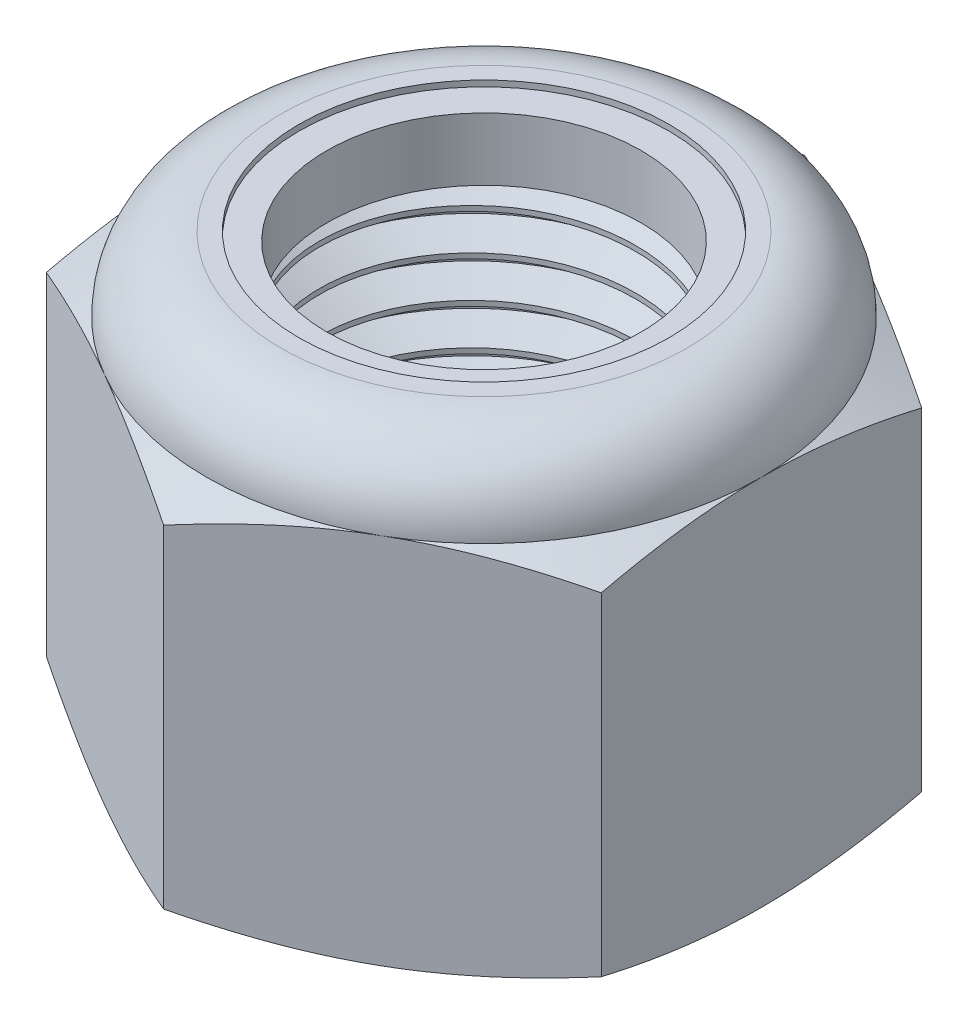
SolidWorks part; units mm, degrees
ref_plane "Front" through (0, 0, 0) normal (0, 0, 1) x (1, 0, 0)
ref_plane "Top" through (0, 0, 0) normal (0, 1, 0) x (1, 0, 0)
ref_plane "Right" through (0, 0, 0) normal (1, 0, 0) x (0, 0, -1)
sketch "Sketch1" plane through (0, 0, 0) normal (1, 0, 0) x (0, 0, -1)
  line L0 (0, 0) -> (0, 11.5094) construction
  line L1 (7.1437, 0) -> (-7.1437, 0) construction
  line L2 (-4.7625, 11.5094) -> (4.7625, 11.5094) construction
  line L3 (4.7625, 11.5094) -> (4.7625, 10.451) construction
  point P9 (-4.7625, 11.5094)
  point P10 (4.7625, 11.5094)
  point P11 (7.1437, 0)
  dimension "Height" = 11.5094
  dimension "Hex Flats" = 14.2875
  dimension "Thread Dia" = 9.525
  dimension "Thread Pitch" = 1.0583
sketch "Sketch13" plane through (0, 0, 0) normal (0, 1, 0) x (1, 0, 0)
  line L1 (0, 8.2489) -> (-7.1438, 4.1244)
  line L2 (-7.1438, 4.1244) -> (-7.1437, -4.1244)
  line L3 (-7.1437, -4.1244) -> (0, -8.2489)
  line L4 (0, -8.2489) -> (7.1438, -4.1244)
  line L5 (7.1438, -4.1244) -> (7.1438, 4.1244)
  line L6 (7.1438, 4.1244) -> (0, 8.2489)
  circle A0 centre (0, 0) radius 7.1437 construction
  circle A1 centre (0, 0) radius 4.7625
  point P11 (0, -4.7625)
  point P13 (0, 4.7625)
extrude "Extrude1" add sketch "Sketch13" along normal up to vertex (11.5094 mm away) up to point (0, 11.5094, 0)
sketch "Sketch5" plane through (0, 0, 0) normal (1, 0, 0) x (0, 0, -1)
  line L0 (0, 0) -> (7.1437, 0)
  line L1 (7.1437, 0) -> (8.2489, 0.5153)
  line L2 (8.2489, 0.5153) -> (8.2489, 9.0758)
  line L3 (8.2489, 9.0758) -> (7.1437, 9.5911)
  line L4 (5.2255, 11.5094) -> (5.2255, 12.7794)
  line L5 (5.2255, 12.7794) -> (9.5189, 12.7794)
  line L6 (9.5189, 12.7794) -> (9.5189, -1.27)
  line L7 (9.5189, -1.27) -> (0, -1.27)
  line L8 (0, -1.27) -> (0, 0)
  line L9 (7.1437, 9.5911) -> (7.1437, 0) construction
  line L12 (8.2489, 11.5094) -> (8.2489, 0) construction
  line L13 (8.2489, 5.7547) -> (9.5189, 5.7547) construction
  line L15 (0, 0) -> (0, 12.7794) construction
  line L18 (7.1437, 0) -> (-7.1437, 0) construction
  line L19 (4.1244, 11.5094) -> (8.2489, 11.5094) construction
  line L20 (0, 12.7794) -> (5.2255, 12.7794) construction
  line L21 (4.1244, 0) -> (8.2489, 0) construction
  arc A0 (7.1437, 9.5911) -> (5.2255, 11.5094) centre (5.2255, 9.5911) ccw
  dimension "D1" = 25
  dimension "D2" = 1.27
  dimension "D4" = 1.9182
revolve "Cut-Revolve3" cut sketch "Sketch5" angle 360 about L15
sketch "Sketch4" plane through (0, 0, 0) normal (1, 0, 0) x (0, 0, -1)
  line L0 (0, 9.5911) -> (5.2388, 9.5911)
  line L1 (5.2388, 9.5911) -> (0, 7.1483)
  line L3 (0, 2.4429) -> (5.2388, 0)
  line L4 (5.2388, 0) -> (0, 0)
  line L5 (0, 0) -> (0, 9.5911) construction
  line L10 (0, 0) -> (0, 11.5094) construction
  line L11 (0, 2.4429) -> (0, 0)
  line L12 (0, 9.5911) -> (0, 7.1483)
  line L13 (6.1867, 9.5911) -> (0, 9.5911) construction
  dimension "D1" = 25
  dimension "D2" = 10.4775
sketch "Sketch6" plane through (0, 0, 0) normal (1, 0, 0) x (0, 0, -1)
  line L0 (0, 9.5911) -> (6.9914, 9.5911)
  line L1 (5.2255, 11.357) -> (2.6128, 11.357)
  line L2 (0, 12.7794) -> (0, 9.5911)
  line L3 (2.6128, 12.7794) -> (0, 12.7794)
  line L4 (0, 12.7794) -> (5.2255, 12.7794) construction
  line L5 (0, 0) -> (0, 12.7794) construction
  line L6 (0, 12.7794) -> (0, 0) construction
  line L7 (2.6128, 11.357) -> (2.6128, 12.7794)
  line L8 (5.2255, 11.5094) -> (5.2255, 11.357) construction
  line L9 (2.6128, 11.357) -> (0, 11.357) construction
  line L10 (0, 11.357) -> (0, 7.1483) construction
  arc A0 (6.9914, 9.5911) -> (5.2255, 11.357) centre (5.2255, 9.5911) ccw
  arc A1 (7.1437, 9.5911) -> (5.2255, 11.5094) centre (5.2255, 9.5911) ccw construction
  dimension "D1" = 0.1524
revolve "Cut-Revolve4" cut sketch "Sketch6" angle 360 about L6
revolve "Cut-Revolve2" cut sketch "Sketch4" angle 360 about L5
sketch "Sketch7" plane through (0, 0, 0) normal (1, 0, 0) x (0, 0, -1)
  line L0 (4.0481, 9.6673) -> (6.9134, 9.6673)
  line L1 (5.2255, 11.2808) -> (4.0481, 11.2808)
  line L2 (4.0481, 11.2808) -> (4.0481, 9.6673)
  line L3 (4.0481, 9.6673) -> (0, 9.6673) construction
  line L4 (0, 9.6673) -> (0, 11.2808) construction
  line L5 (0, 11.2808) -> (4.0481, 11.2808) construction
  line L6 (4.0481, 9.6673) -> (4.0481, 9.5911) construction
  line L7 (0, 9.5911) -> (6.9914, 9.5911) construction
  line L8 (5.2255, 11.2808) -> (5.2255, 11.357) construction
  arc A0 (6.9134, 9.6673) -> (5.2255, 11.2808) centre (5.2255, 9.5911) ccw
  arc A2 (6.9914, 9.5911) -> (5.2255, 11.357) centre (5.2255, 9.5911) ccw construction
  point P15 (4.0481, 11.2808)
  point P18 (-4.6368, 11.2808)
  point P19 (4.6368, 11.2808)
  dimension "D1" = 0.0762
  dimension "D2" = 8.0962
revolve "Revolve2" add sketch "Sketch7" angle 360 about L4
sketch "Sketch2" plane through (0, 0, 0) normal (1, 0, 0) x (0, 0, -1)
  line L0 (-4.7625, 0) -> (-4.7625, 9.5911) construction
  line L1 (0, 0) -> (4.7625, 0)
  line L2 (0, 0) -> (0, 9.5911)
  line L3 (0, 9.5911) -> (4.7625, 9.5911)
  line L4 (4.7625, 0) -> (4.7625, 9.5911)
  line L6 (6.1867, 9.5911) -> (7.1437, 9.5911) construction
  line L7 (0, -4.7625) -> (0, 0) construction
revolve "Revolve1" add sketch "Sketch2" angle 360 about L7
sketch "Sketch9" plane through (0, 0, 0) normal (1, 0, 0) x (0, 0, -1)
  line L0 (4.8771, 10.5833) -> (4.8771, 9.525) construction
  line L1 (4.8771, 9.525) -> (3.9605, 10.0542) construction
  line L2 (3.9605, 10.0542) -> (4.8771, 10.5833) construction
  line L3 (4.0751, 10.1203) -> (4.0751, 9.988) construction
  line L4 (4.7625, 10.5172) -> (4.7625, 9.5911) construction
  line L5 (3.9605, 10.0542) -> (4.0751, 10.0542) construction
  line L6 (4.7625, 10.0542) -> (4.8771, 10.0542) construction
  line L7 (4.8198, 10.0542) -> (4.8198, 10.5503) construction
  line L8 (4.8771, 9.525) -> (4.8198, 10.5503)
  line L9 (4.8198, 10.5503) -> (4.0751, 10.1203)
  line L10 (4.0751, 10.1203) -> (4.0751, 9.988)
  line L11 (4.0751, 9.988) -> (4.8771, 9.525)
  dimension "D1" = 1.0583
  dimension "D2" = 0.1323
sketch "Sketch10" plane through (0, 9.5911, 0) normal (0, 1, 0) x (1, 0, 0)
  circle A1 centre (0, 0) radius 4.7625
  circle A2 centre (0, 0) radius 4.7625
  dimension "D1" = 0
curve "Helix/Spiral1" pitch 1.0583 height 12.5677 turns 11.875
sweep "Cut-Sweep1" cut profiles "Sketch9" path "Helix/Spiral1"
sketch "Sketch11" plane through (0, 0, 0) normal (1, 0, 0) x (0, 0, -1)
  line L0 (0, 0) -> (0, 11.5094) construction
  line L1 (7.1437, 0) -> (-7.1437, 0) construction
  line L4 (0, 11.5094) -> (0, 0) construction
  line L5 (0, 5.7547) -> (4.7625, 5.7547) construction
  line L6 (0, 0) -> (5.2388, 0)
  line L7 (0, 2.4429) -> (0, 0)
  line L8 (5.2388, 0) -> (0, 2.4429)
  dimension "D1" = 10.4775
  dimension "D2" = 25
revolve "Revolve3" add sketch "Sketch11" angle 360 about L4
sketch "Sketch12" plane through (0, 0, 0) normal (1, 0, 0) x (0, 0, -1)
  line L0 (5.2388, 9.5911) -> (0, 9.5911)
  line L1 (0, 9.5911) -> (0, 0)
  line L2 (0, 0) -> (5.2388, 0)
  line L3 (7.1437, 0) -> (-7.1437, 0) construction
  line L4 (5.2388, 0) -> (5.2388, 9.5911)
  line L5 (-5.2388, 0) -> (5.2388, 0) construction
revolve "Revolve4" add sketch "Sketch12" angle 360 about L0
combine bodies "Combine1" bodies to combine 136 133
equation "\"D4@Sketch5\" = \"Height@Sketch1\" / 6"
equation "\"D1@Sketch9\" = \"Thread Pitch@Sketch1\""
equation "\"D2@Sketch9\" = \"Thread Pitch@Sketch1\" / 8"
equation "\"D4@Helix/Spiral1\" = \"Thread Pitch@Sketch1\""
equation "\"D3@Helix/Spiral1\" = \"Thread Pitch@Sketch1\" + \"Height@Sketch1\""
equation "\"D2@Sketch4\" = \"Thread Dia@Sketch1\" * 1.1"
equation "\"D1@Sketch11\" = \"Thread Dia@Sketch1\" * 1.1"
equation "\"D2@Sketch7\" = \"Thread Dia@Sketch1\" * .85"
